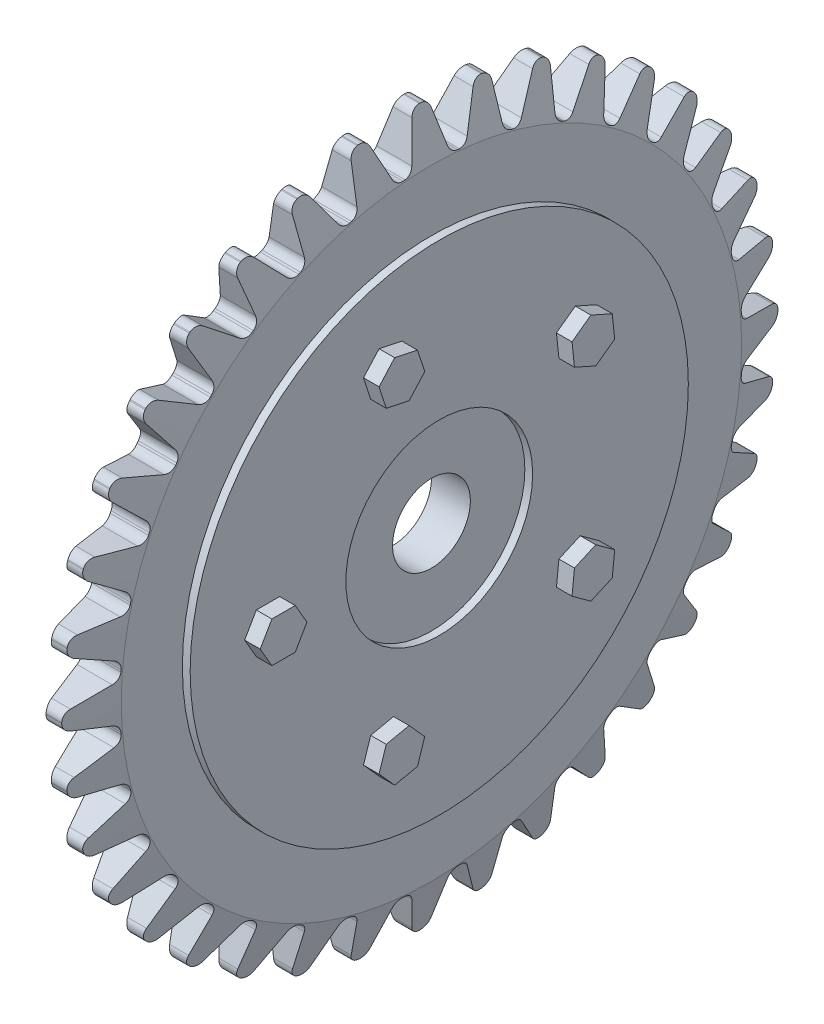
SolidWorks part; units mm, degrees
material "AISI 8620 Steel, carburized"
ref_plane "Front Plane" through (0, 0, 0) normal (1, 0, 0) x (0, 1, 0)
ref_plane "Top Plane" through (0, 0, 0) normal (0, 0, 1) x (0, 1, 0)
ref_plane "Right Plane" through (0, 0, 0) normal (0, 1, 0) x (-1, 0, 0)
sketch "Sketch1" plane through (0, 0, 0) normal (1, 0, 0) x (0, 1, 0)
  line L0 (-54.6163, 0) -> (60.4641, 0) construction
  line L1 (0, 55.8079) -> (0, -55.6093) construction
  line L2 (-1.2228, 45.088) -> (-2.5, 39.9218)
  line L3 (-2.5981, 20.5) -> (0, 19)
  line L4 (0, 19) -> (2.5981, 20.5)
  line L5 (2.5981, 20.5) -> (2.5981, 23.5)
  line L6 (2.5981, 23.5) -> (0, 25)
  line L7 (0, 25) -> (-2.5981, 23.5)
  line L8 (-2.5981, 23.5) -> (-2.5981, 20.5)
  line L9 (1.2228, 45.088) -> (2.5, 39.9218)
  circle A1 centre (0, 0) radius 5
  circle A2 centre (0, 0) radius 12
  circle A3 centre (0, 0) radius 40
  circle A4 centre (0, 0) radius 38
  circle A5 centre (0, 0) radius 32
  arc A6 (-46, 0) -> (46, 0) centre (0, 0) ccw
  circle A7 centre (0, 0) radius 22 construction
  circle A8 centre (0, 22) radius 2.5981 construction
  arc A9 (-3.3554, 39.859) -> (-2.2911, 40.7668) centre (-3.456, 41.0548) ccw
  arc A10 (3.3554, 39.859) -> (2.2911, 40.7668) centre (3.456, 41.0548) cw
  arc A11 (0.0594, 46) -> (-0.0594, 46) centre (0, 0) ccw
  arc A12 (1.2228, 45.088) -> (0.0594, 46) centre (0.0579, 44.8) ccw
  arc A13 (-1.2228, 45.088) -> (-0.0594, 46) centre (-0.0579, 44.8) cw
  point P35 (1, 45.9891)
  point P38 (-1, 45.9891)
  dimension "D1" = 80
  dimension "D2" = 10
  dimension "D3" = 24
  dimension "D5" = 76
  dimension "D6" = 92
  dimension "D7" = 44
  dimension "D8" = 3
  dimension "D11" = 1.2
  dimension "D12" = 1.2
  dimension "D9" = 5
  dimension "D10" = 2
  dimension "D4" = 20
extrude "Boss-Extrude1" add sketch "Sketch1" along normal mid plane 5 contours A3 A4 | A4 | A1 region at (0, 0, 38.8686)
extrude "Boss-Extrude2" add sketch "Sketch1<3>" along normal mid plane 7 contours A5 | A2
sketch "Sketch1<3>" plane through (0, 0, 0) normal (1, 0, 0) x (0, 1, 0) same geometry as "Sketch1"
extrude "Boss-Extrude3" add sketch "Sketch1<4>" along normal mid plane 11 contours L6 L7 L8 L3 L4 L5
sketch "Sketch1<4>" plane through (0, 0, 0) normal (1, 0, 0) x (0, 1, 0) same geometry as "Sketch1"
pattern_circular "CirPattern1" count 5 over 360 about axis through (3.5, 0, 0) along (1, 0, 0) of "Boss-Extrude3"
extrude "Boss-Extrude4" add sketch "Sketch1<5>" along normal mid plane 5 contours A13 L2 A3 L9 A12 A11 | A9 A3 L2 | A3 A10 L9 region at (0, 0, 42.5039) region at (0, -2.6385, 40.0912) region at (0, 2.6385, 40.0912)
sketch "Sketch1<5>" plane through (0, 0, 0) normal (1, 0, 0) x (0, 1, 0) same geometry as "Sketch1"
pattern_circular "CirPattern2" count 36 over 360 about axis through (-2.5, 0, 0) along (1, 0, 0) of "Boss-Extrude4"
sketch "Sketch3" plane through (-2.5, 0, 0) normal (-1, 0, 0) x (0, -1, 0)
  line L0 (3.4862, 39.8478) -> (-5.2374, 39.8478) construction
  line L1 (0.0594, 46) -> (-2.426, 46) construction
  arc A0 (3.6171, 39.8361) -> (3.3554, 39.859) centre (0, 0) ccw construction
sketch "Sketch2" plane through (0, 0, 0) normal (0, 1, 0) x (-1, 0, 0)
  line L0 (-2.5, 46) -> (2.5, 46) construction
  line L1 (-2.5, 46) -> (2.5, 46)
  line L2 (-2.5, 46) -> (-2.5, 32)
  line L3 (-2.5, -32) -> (-2.5, -46)
  line L4 (0, 47.8987) -> (0, 29.2015) construction
  line L5 (-2.5, 46) -> (-2.5, 39.85)
  line L6 (2.5, 46) -> (2.5, 32)
  line L7 (2.5, -32) -> (2.5, -46)
  line L8 (-2.5, 39.85) -> (-1, 46)
  line L9 (2.5, 46) -> (2.5, 39.85)
  line L10 (2.5, 39.85) -> (1, 46)
  line L11 (2.5, 46) -> (2.5, 39.85)
  line L12 (-9.4539, 0) -> (14.2455, 0) construction
  line L13 (-2.9582, 46.3587) -> (3.2737, 46.3587)
  line L14 (-1, 46) -> (-0.8895, 46.4532)
  line L15 (-2.5, 46) -> (-2.5, 46.4532)
  line L16 (-2.5, 46.4532) -> (-0.8895, 46.4532)
  line L17 (1, 46) -> (0.8895, 46.4532)
  line L18 (2.5, 46.4532) -> (0.8895, 46.4532)
  line L19 (2.5, 46) -> (2.5, 46.4532)
  dimension "D1" = 1
  dimension "D2" = 6.15
revolve "Cut-Revolve1" cut sketch "Sketch2" angle 360 about L12 region at (1.7279, 0, 46.181) region at (2, 0, 43.95) region at (-1.7279, 0, 46.1811) region at (-2, 0, 43.95)
